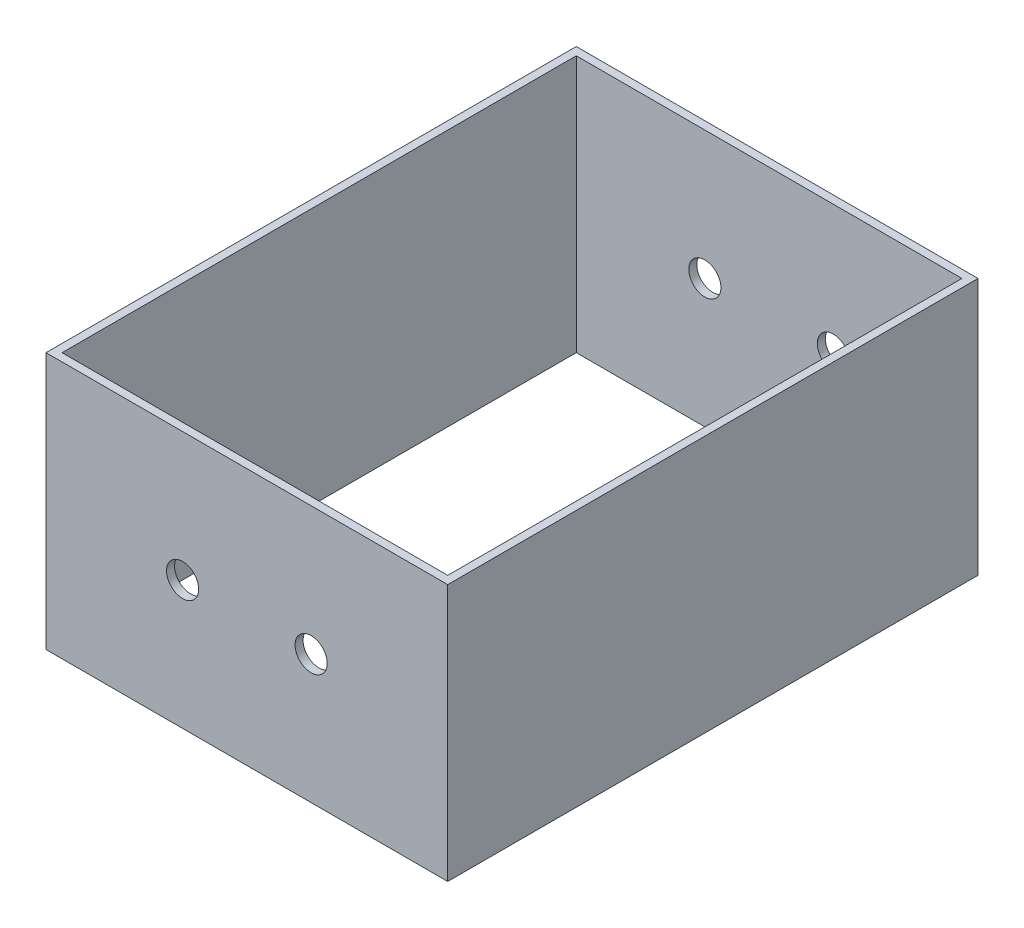
SolidWorks part; units mm, degrees
ref_plane "Front Plane" through (0, 0, 0) normal (0, 0, 1) x (1, 0, 0)
ref_plane "Top Plane" through (0, 0, 0) normal (0, 1, 0) x (1, 0, 0)
ref_plane "Right Plane" through (0, 0, 0) normal (1, 0, 0) x (0, 0, -1)
sketch "Sketch1" plane through (0, 0, 0) normal (0, 1, 0) x (1, 0, 0)
  line L1 (-76.2, -101.6) -> (76.2, -101.6)
  line L2 (-76.2, -101.6) -> (-76.2, 101.6)
  line L3 (-76.2, 101.6) -> (76.2, 101.6)
  line L4 (76.2, -101.6) -> (76.2, 101.6)
  line L5 (-76.2, -101.6) -> (76.2, 101.6) construction
  line L6 (-76.2, 101.6) -> (76.2, -101.6) construction
  point P0 (0, 0)
  dimension "D1" = 152.4
  dimension "D2" = 203.2
extrude "Boss-Extrude1" add sketch "Sketch1" along normal blind 101.6
shell "Shell1" thickness 3.175 removed face at (0, 0, 0) removed face at (0, 101.6, 0) outward yes
sketch "Sketch2" plane through (0, 0, 104.775) normal (0, 0, 1) x (1, 0, 0)
  line L2 (-79.375, 101.6) -> (-79.375, 0) construction
  line L3 (79.375, 101.6) -> (79.375, 0) construction
  line L4 (-79.375, 50.8) -> (79.375, 50.8) construction
  line L5 (0, 50.8) -> (0, 0) construction
  circle A0 centre (-25.4, 50.8) radius 6.35
  circle A1 centre (25.4, 50.8) radius 6.35
  point P0 (0, 50.8)
  point P1 (-25.4, 50.8)
  dimension "D2" = 12.7
  dimension "D1" = 25.4
extrude "Cut-Extrude1" cut sketch "Sketch2" against normal through all both and the other way through all
